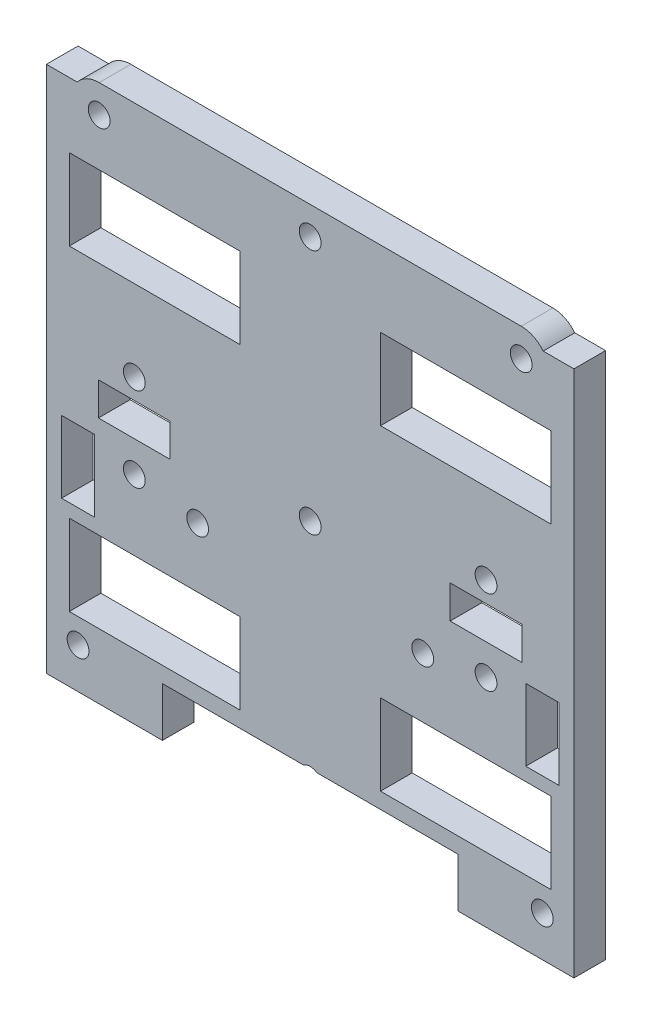
SolidWorks part; units mm, degrees
ref_plane "Front Plane" through (0, 0, 0) normal (0, 0, 1) x (1, 0, 0)
ref_plane "Top Plane" through (0, 0, 0) normal (0, 1, 0) x (1, 0, 0)
ref_plane "Right Plane" through (0, 0, 0) normal (1, 0, 0) x (0, 0, -1)
sketch "Sketch1" plane through (0, 0, 0) normal (0, 0, 1) x (1, 0, 0)
  line L0 (0, -37.5) -> (0, 37.5) construction
  line L1 (-47.5, -37.5) -> (47.5, -37.5)
  line L2 (-47.5, -37.5) -> (-47.5, 37.5)
  line L3 (-47.5, 37.5) -> (47.5, 37.5)
  line L4 (47.5, -37.5) -> (47.5, 37.5)
  line L5 (-47.5, -37.5) -> (47.5, 37.5) construction
  line L6 (-47.5, 37.5) -> (47.5, -37.5) construction
  line L7 (-47.5, 0) -> (47.5, 0) construction
  line L8 (-47.5, 22.5) -> (47.5, 22.5) construction
  line L9 (34.25, 16.75) -> (10, 28.25) construction
  line L10 (-34.25, 28.25) -> (-10, 28.25)
  line L11 (-34.25, 28.25) -> (-34.25, 16.75)
  line L12 (-34.25, 16.75) -> (-10, 16.75)
  line L13 (-10, 28.25) -> (-10, 16.75)
  line L14 (-34.25, 28.25) -> (-10, 16.75) construction
  line L15 (-34.25, 16.75) -> (-10, 28.25) construction
  line L16 (34.25, 28.25) -> (10, 16.75) construction
  line L17 (10, 28.25) -> (10, 16.75)
  line L18 (34.25, 16.75) -> (10, 16.75)
  line L19 (34.25, 28.25) -> (34.25, 16.75)
  line L20 (34.25, 28.25) -> (10, 28.25)
  line L21 (34.25, -28.25) -> (10, -16.75) construction
  line L22 (-34.25, -16.75) -> (-10, -28.25) construction
  line L23 (-34.25, -28.25) -> (-10, -16.75) construction
  line L24 (34.25, -16.75) -> (10, -28.25) construction
  line L25 (34.25, -28.25) -> (10, -28.25)
  line L26 (34.25, -28.25) -> (34.25, -16.75)
  line L27 (34.25, -16.75) -> (10, -16.75)
  line L28 (10, -28.25) -> (10, -16.75)
  line L29 (-10, -28.25) -> (-10, -16.75)
  line L30 (-34.25, -16.75) -> (-10, -16.75)
  line L31 (-34.25, -28.25) -> (-34.25, -16.75)
  line L32 (-34.25, -28.25) -> (-10, -28.25)
  point P0 (0, 0)
  point P12 (-22.125, 22.5)
  point P21 (22.125, 22.5)
  point P30 (22.125, -22.5)
  point P31 (-22.125, -22.5)
  dimension "D1" = 95
  dimension "D2" = 75
  dimension "D3" = 22.5
  dimension "D4" = 24.25
  dimension "D5" = 11.5
  dimension "D6" = 10
extrude "Boss-Extrude1" add sketch "Sketch1" along normal blind 4.5
sketch "Sketch8" plane through (0, 0, 4.5) normal (0, 0, 1) x (1, 0, 0)
  line L0 (-47.5, 37.5) -> (-47.5, -37.5) construction
  line L1 (47.5, -37.5) -> (47.5, 37.5) construction
  circle A0 centre (-47.5, 29.5) radius 8
  circle A1 centre (47.5, 29.5) radius 8
  dimension "D1" = 16
extrude "Boss-Extrude2" [suppressed] add sketch "Sketch8" against normal through all
sketch "Sketch2" plane through (0, 0, 4.5) normal (0, 0, 1) x (1, 0, 0)
  line L0 (0, -37.5) -> (0, 37.5) construction
  line L1 (-47.5, -37.5) -> (47.5, -37.5) construction
  line L2 (47.5, 37.5) -> (-47.5, 37.5) construction
  line L3 (-47.5, 0) -> (47.5, 0) construction
  line L4 (-47.5, 37.5) -> (-47.5, -37.5) construction
  line L5 (47.5, -37.5) -> (47.5, 37.5) construction
  line L6 (-40, 0) -> (40, 0) construction
  line L7 (-30, 35) -> (30, 35) construction
  circle A0 centre (-30, 35) radius 1.55
  circle A1 centre (30, 35) radius 1.55
  circle A2 centre (40, 0) radius 1.55
  circle A3 centre (-40, 0) radius 1.55
  circle A4 centre (0, 35) radius 1.55
  dimension "D1" = 3.1
  dimension "D7" = 3.1
  dimension "D8" = 3.1
  dimension "D9" = 3.1
  dimension "D2" = 30
  dimension "D3" = 35
  dimension "D4" = 80
  dimension "D5" = 40
  dimension "D6" = 0
extrude "screwHoles" cut sketch "Sketch2" against normal through all
sketch "Sketch3" plane through (0, 0, 4.5) normal (0, 0, 1) x (1, 0, 0)
  line L0 (-47.5, -20) -> (26.0486, -20) construction
  line L1 (-47.5, 37.5) -> (-47.5, -37.5) construction
  line L3 (0, 37.5) -> (0, -37.5) construction
  line L4 (47.5, 37.5) -> (-47.5, 37.5) construction
  line L5 (-47.5, -37.5) -> (47.5, -37.5) construction
  line L6 (19.1, -22.35) -> (8.9, -17.65) construction
  line L7 (-19.1, -17.65) -> (-8.9, -17.65)
  line L8 (-19.1, -17.65) -> (-19.1, -22.35)
  line L9 (-19.1, -22.35) -> (-8.9, -22.35)
  line L10 (-8.9, -17.65) -> (-8.9, -22.35)
  line L11 (-19.1, -17.65) -> (-8.9, -22.35) construction
  line L12 (-19.1, -22.35) -> (-8.9, -17.65) construction
  line L13 (19.1, -17.65) -> (8.9, -22.35) construction
  line L14 (8.9, -17.65) -> (8.9, -22.35)
  line L15 (19.1, -22.35) -> (8.9, -22.35)
  line L16 (19.1, -17.65) -> (19.1, -22.35)
  line L17 (19.1, -17.65) -> (8.9, -17.65)
  line L18 (-47.5, 37.5) -> (-47.5, -37.5) construction
  point P2 (-47.5, 0)
  point P12 (-14, -20)
  point P21 (14, -20)
  dimension "D1" = 10.2
  dimension "D2" = 4.7
  dimension "D3" = 14
  dimension "D4" = 20
extrude "BeltClamp" [suppressed] cut sketch "Sketch3" against normal through all
sketch "Sketch4" plane through (0, 0, 4.5) normal (0, 0, 1) x (1, 0, 0)
  line L0 (-47.5, 0) -> (47.5, 0) construction
  line L1 (-47.5, 37.5) -> (-47.5, -37.5) construction
  line L2 (47.5, -37.5) -> (47.5, 37.5) construction
  line L3 (0, 0) -> (0, 33.45) construction
  line L4 (-30.1, 2.35) -> (-19.9, 2.35)
  line L5 (-30.1, 2.35) -> (-30.1, -2.35)
  line L6 (-30.1, -2.35) -> (-19.9, -2.35)
  line L7 (-19.9, 2.35) -> (-19.9, -2.35)
  line L8 (-30.1, 2.35) -> (-19.9, -2.35) construction
  line L9 (-30.1, -2.35) -> (-19.9, 2.35) construction
  line L10 (30.1, -2.35) -> (19.9, 2.35) construction
  line L11 (30.1, 2.35) -> (19.9, -2.35) construction
  line L12 (19.9, 2.35) -> (19.9, -2.35)
  line L13 (30.1, -2.35) -> (19.9, -2.35)
  line L14 (30.1, 2.35) -> (30.1, -2.35)
  line L15 (30.1, 2.35) -> (19.9, 2.35)
  line L16 (-30.1, -2.35) -> (-19.9, 2.35) construction
  circle A0 centre (-40, 0) radius 1.55 construction
  circle A1 centre (0, 35) radius 1.55 construction
  circle A2 centre (0, 0) radius 1.55
  point P6 (-25, 0)
  point P22 (25, 0)
  dimension "D1" = 10.2
  dimension "D2" = 4.7
  dimension "D5" = 3.1
  dimension "D3" = 0
  dimension "D4" = 25
extrude "Cut-Extrude3" cut sketch "Sketch4" against normal through all
sketch "Sketch5" plane through (0, 0, 4.5) normal (0, 0, 1) x (1, 0, 0)
  line L0 (-47.5, -9.75) -> (47.5, -9.75) construction
  line L1 (-47.5, 37.5) -> (-47.5, -37.5) construction
  line L2 (47.5, -37.5) -> (47.5, 37.5) construction
  line L4 (0, -37.5) -> (0, 37.5) construction
  line L5 (-47.5, -37.5) -> (47.5, -37.5) construction
  line L6 (47.5, 37.5) -> (-47.5, 37.5) construction
  line L7 (-30.65, -14.85) -> (-35.35, -4.65) construction
  line L8 (30.65, -4.65) -> (35.35, -4.65)
  line L9 (30.65, -4.65) -> (30.65, -14.85)
  line L10 (30.65, -14.85) -> (35.35, -14.85)
  line L11 (35.35, -4.65) -> (35.35, -14.85)
  line L12 (30.65, -4.65) -> (35.35, -14.85) construction
  line L13 (30.65, -14.85) -> (35.35, -4.65) construction
  line L14 (-30.65, -4.65) -> (-35.35, -14.85) construction
  line L15 (-35.35, -4.65) -> (-35.35, -14.85)
  line L16 (-30.65, -14.85) -> (-35.35, -14.85)
  line L17 (-30.65, -4.65) -> (-30.65, -14.85)
  line L18 (-30.65, -4.65) -> (-35.35, -4.65)
  line L19 (33, -9.75) -> (33, -37.5) construction
  line L20 (-33, -9.75) -> (-33, -37.5) construction
  line L21 (-33, -31.75) -> (33, -31.75) construction
  circle A0 centre (33, -31.75) radius 1.55
  circle A1 centre (-33, -31.75) radius 1.55
  circle A2 centre (0, -31.75) radius 1.55
  point P15 (33, -9.75)
  point P24 (-33, -9.75)
  dimension "D7" = 3.1
  dimension "D5" = 3.1
  dimension "D2" = 10.2
  dimension "D3" = 4.7
  dimension "D4" = 33
  dimension "D6" = 22
  dimension "D1" = 9.75
extrude "Cut-Extrude4" cut sketch "Sketch5" against normal through all
sketch "Sketch9" plane through (0, 0, 4.5) normal (0, 0, 1) x (1, 0, 0)
  line L0 (47.5, 37.5) -> (-47.5, 37.5) construction
  line L1 (0, 37.5) -> (0, -37.5) construction
  line L2 (-47.5, -37.5) -> (47.5, -37.5) construction
  line L3 (50.5, 35) -> (45.5, 35) construction
  line L4 (-50.5, 35) -> (-45.5, 35) construction
  circle A0 centre (-30, 35) radius 4
  circle A1 centre (-30, 35) radius 1.55
  circle A2 centre (-30, 35) radius 1.55 construction
  circle A3 centre (30, 35) radius 1.55
  circle A4 centre (30, 35) radius 4
  point P17 (0, -37.5)
  dimension "D1" = 8
extrude "Boss-Extrude3" add sketch "Sketch9" against normal through all
sketch "Sketch10" plane through (0, 0, 4.5) normal (0, 0, 1) x (1, 0, 0)
  line L0 (-60, 37.5) -> (-37.5, 37.5)
  line L1 (-37.5, 37.5) -> (-37.5, -37.5)
  line L2 (-47.5, -37.5) -> (47.5, -37.5) construction
  line L3 (-37.5, -37.5) -> (-60, -37.5)
  line L4 (-60, -37.5) -> (-60, 37.5)
  line L5 (0, 37.5) -> (0, -37.5) construction
  line L6 (26.8775, 37.5) -> (-26.8775, 37.5) construction
  line L7 (60, -37.5) -> (60, 37.5)
  line L8 (37.5, -37.5) -> (60, -37.5)
  line L9 (37.5, 37.5) -> (37.5, -37.5)
  line L10 (60, 37.5) -> (37.5, 37.5)
  line L11 (-60, -37.5) -> (-60, 37.5)
  line L12 (-33.1225, 37.5) -> (-47.5, 37.5) construction
  line M3 (47.5, -37.5) -> (47.5, 37.5)
  line M7 (-47.5, 37.5) -> (-47.5, -37.5)
  line M8 (-47.5, -37.5) -> (47.5, -37.5)
  dimension "D3" = 0
  dimension "D1" = 75
  dimension "D2" = 60
extrude "Cut-Extrude5" cut sketch "Sketch10" against normal through all contours L1 L0 M7 M8 | L10 L9 M3 M8 region at (42.5, 0, 4.5) region at (-42.5, 0, 4.5)
sketch "Sketch11" plane through (0, 0, 4.5) normal (0, 0, 1) x (1, 0, 0)
  line L0 (-30, 39) -> (30, 39)
  line L1 (30, 39) -> (26.8775, 37.5)
  line L2 (26.8775, 37.5) -> (-26.8775, 37.5)
  line L3 (-26.8775, 37.5) -> (-30, 39)
  arc A0 (-26.8775, 37.5) -> (-33.1225, 37.5) centre (-30, 35) ccw construction
  arc A1 (33.1225, 37.5) -> (26.8775, 37.5) centre (30, 35) ccw construction
extrude "Boss-Extrude4" add sketch "Sketch11" against normal through all
sketch "Sketch12" plane through (0, 0, 4.5) normal (0, 0, 1) x (1, 0, 0)
  line L0 (-37.5, -8.25) -> (37.5, -8.25) construction
  line L1 (-37.5, 37.5) -> (-37.5, -37.5) construction
  line L2 (37.5, 37.5) -> (37.5, -37.5) construction
  line L3 (0, 0) -> (0, -37.5) construction
  line L4 (-37.5, -37.5) -> (37.5, -37.5) construction
  circle A0 centre (-16, -8.25) radius 1.55
  circle A1 centre (16, -8.25) radius 1.55
  dimension "D2" = 3.1
  dimension "D1" = 16
  dimension "D3" = 8.25
extrude "FanBraceScrews" cut sketch "Sketch12" against normal through all
sketch "Sketch13" plane through (0, 0, 4.5) normal (0, 0, 1) x (1, 0, 0)
  line L0 (-37.5, -37.5) -> (37.5, -37.5) construction
  line L1 (-21, -44.5) -> (21, -44.5)
  line L2 (-21, -44.5) -> (-21, -30.5)
  line L3 (-21, -30.5) -> (21, -30.5)
  line L4 (21, -44.5) -> (21, -30.5)
  line L5 (-21, -44.5) -> (21, -30.5) construction
  line L6 (-21, -30.5) -> (21, -44.5) construction
  point P0 (0, -37.5)
  dimension "D1" = 42
  dimension "D2" = 7
extrude "Cut-Extrude7" cut sketch "Sketch13" against normal through all
sketch "Sketch14" plane through (0, 0, 4.5) normal (0, 0, 1) x (1, 0, 0)
  line L0 (16, -9.8) -> (16, 3.75) construction
  line L1 (0, 0) -> (0, -40.3958) construction
  line L2 (-16, -9.8) -> (-16, 3.75) construction
  circle A0 centre (16, -8.25) radius 1.55 construction
  circle A1 centre (16, 3.75) radius 1.55
  circle A2 centre (-16, 3.75) radius 1.55
  dimension "D2" = 3.1
  dimension "D1" = 12
extrude "Cut-Extrude8" [suppressed] cut sketch "Sketch14" against normal through all
sketch "Sketch15" plane through (0, 0, 4.5) normal (0, 0, 1) x (1, 0, 0)
  line L0 (-25, 5.25) -> (-25, -6.75) construction
  line L2 (0, 0) -> (0, -11.0705) construction
  line L3 (16, -8.3509) -> (25, -6.75) construction
  line L4 (25, 5.25) -> (25, -6.75) construction
  circle A0 centre (-25, 5.25) radius 1.55
  circle A1 centre (-25, -6.75) radius 1.55
  circle A2 centre (25, -6.75) radius 1.55
  circle A3 centre (25, 5.25) radius 1.55
  circle A5 centre (-16, -8.25) radius 1.55 construction
  dimension "D1" = 12
  dimension "D3" = 3.1
  dimension "D4" = 3.1
  dimension "D2" = 25
  dimension "D5" = 1.5
extrude "BeltClipScrews" cut sketch "Sketch15" against normal through all
equation "\"X-ROD-SPACING\"=45"
equation "\"Y-ROD-SPACING\"=75"
equation "\"Z-ROD-SPACING\"=17.5"
equation "\"Y-BED-OFFSET\"=2"
equation "\"Y-BED-ROD-INSET\"=3.5"
equation "\"Y-BED-SCREW-SPACING\"=209"
equation "\"Y-BED-SCREW-CUTOUT-SLOT-HEIGHT\"=2"
equation "\"T-SLOT-NUT-FILLET-RADIUS\"=0.25"
equation "\"T-SLOT-SCREW-SHAFT-RADIUS\"=1.75"
equation "\"T-SLOT-SCREW-SHAFT-CUTOUT-LENGTH\"=10.5"
equation "\"T-SLOT-NUT-DEPTH\"=4.2"
equation "\"T-SLOT-NUT-WIDTH\"=3"
equation "\"T-SLOT-NUT-END-DISTANCE\"=8"
equation "\"ACRYLIC-THICKNESS\"=10"
equation "\"ACRYLIC-THICKNESS2\"=4.5"
equation "\"ACRYLIC-TAB-CUTOUT-SIZE\"=\"ACRYLIC-THICKNESS\"+\"ACRYLIC-TAB-TOLERANCE\"*2"
equation "\"ACRYLIC-TAB-WIDTH\"=\"ACRYLIC-THICKNESS\""
equation "\"ACRYLIC-M3-HOLE\"=3.1"
equation "\"SMOOTHROD-CAP-SCREW-DISTANCE\"=20"
equation "\"FRAME-WIDTH-INNER\"=370"
equation "\"NEMA17-HOLE-SPACING\"=31"
equation "\"NEMA17-CENTRAL-CUTOUT\"=22.5"
equation "\"Z-BRACKET-REACH\"=55"
equation "\"Z-ROD-INSET\"=16"
equation "\"TOP-BRACKET-SPACING\"=40"
equation "\"SMOOTHROD-X-LENGTH\"=350"
equation "\"SMOOTHROD-Y-LENGTH\"=350"
equation "\"SMOOTHROD-Z-LENGTH\"=350"
equation "\"SMOOTHROD-TIGHTENING-HEADROOM\"=.25"
equation "\"LEADSCREW-Z-LENGTH\"=300"
equation "\"SCREW-LENGTH-FRAME\"=\"ACRYLIC-THICKNESS\" + 10"
equation "\"SCREW-LENGTH-MOTOR\"=\"ACRYLIC-THICKNESS\" + 5"
equation "\"SCREW-HEAD-RADIUS\"=6"
equation "\"PRINTED-X-SMOOTHROD-DIAMETER\"=8.2"
equation "\"PRINTED-X-SMOOTHROD-CUTOUT\"=10"
equation "\"PRINTED-X-BASE-HEIGHT\"=10"
equation "\"PRINTED-LM8UU-CUTOUT-SIZE\"=15.25"
equation "\"PRINTED-LM8UU-CUTOUT-LENGTH\"=24.5"
equation "\"PRINTED-X-IDLER-HEIGHT\"=16"
equation "\"PSU-MOUNTING-WIDTH\"=95"
equation "\"PSU-MOUNTING-HEIGHT\"=177"
equation "\"Y-BELT-TO-ROD-DISTANCE\"=20"
equation "\"SPOOL-HOLDER-ROD-SPACING\"=150"
equation "\"D3@Sketch1\"=\"X-ROD-SPACING\"/2"
equation "\"D4@Sketch1\"=\"ACRYLIC-X-CARRIAGE-LM8UU-CUTOUT-WIDTH\""
equation "\"D1@Boss-Extrude1\"=\"ACRYLIC-THICKNESS2\""
equation "\"D1@Sketch2\"=\"ACRYLIC-M3-HOLE\""
equation "\"D1@Sketch3\"=\"ACRYLIC-TAB-CUTOUT-SIZE\""
equation "\"D2@Sketch3\"=\"ACRYLIC-THICKNESS2\"+\"ACRYLIC-TAB-TOLERANCE\"*2"
equation "\"ACRYLIC-X-CARRIAGE-WIDTH\"=55"
equation "\"ACRYLIC-X-CARRIAGE-HEIGHT\"=75"
equation "\"D2@Sketch1\"=\"ACRYLIC-X-CARRIAGE-HEIGHT\""
equation "\"ACRYLIC-X-CARRIAGE-CENTER-TAB-SPACING\"=14"
equation "\"D3@Sketch3\"=\"ACRYLIC-X-CARRIAGE-CENTER-TAB-SPACING\""
equation "\"SCREW-LENGTH-EXTRUDER\"=28"
equation "\"ACRYLIC-X-CARRIAGE-SCREW-SPACING-X\"=15"
equation "\"ACRYLIC-X-CARRIAGE-SCREW-SPACING-Y\"=33"
equation "\"D1@Sketch4\"=\"ACRYLIC-TAB-CUTOUT-SIZE\""
equation "\"D2@Sketch4\"=\"ACRYLIC-THICKNESS2\"+\"ACRYLIC-TAB-TOLERANCE\"*2"
equation "\"D2@Sketch5\"=\"ACRYLIC-TAB-CUTOUT-SIZE\""
equation "\"D3@Sketch5\"=\"ACRYLIC-THICKNESS2\"+\"ACRYLIC-TAB-TOLERANCE\"*2"
equation "\"ACRYLIC-X-CARRIAGE-EXTRUDER-SHELF-DEPTH\"=\"ACRYLIC-X-CARRIAGE-EXTRUDER-OFFSET\" + 28"
equation "\"ACRYLIC-X-CARRIAGE-EXTRUDER-BRACE-SPACING\"=23"
equation "\"D4@Sketch5\"=\"ACRYLIC-X-CARRIAGE-DUAL-MOUNT-BRACE-WIDTH\""
equation "\"D1@Sketch5\"=\"ACRYLIC-THICKNESS2\"/2 + 7.5"
equation "\"D4@Sketch2\"=\"ACRYLIC-X-CARRIAGE-DUAL-MOUNT-SCREW-WIDTH\"*2"
equation "\"D5@Sketch2\"=\"ACRYLIC-X-CARRIAGE-DUAL-MOUNT-SCREW-WIDTH\""
equation "\"D7@Sketch2\"=\"ACRYLIC-M3-HOLE\""
equation "\"D8@Sketch2\"=\"ACRYLIC-M3-HOLE\""
equation "\"ACRYLIC-X-CARRIAGE-LM8UU-CUTOUT-WIDTH\"=24.25"
equation "\"ACRYLIC-TAB-TOLERANCE\"=.1"
equation "\"ACRYLIC-X-CARRIAGE-EXTRUDER-OFFSET\"=26"
equation "\"ACRYLIC-X-CARRIAGE-EXTRUDER-ANGLE\"=90"
equation "\"ACRYLIC-X-CARRIAGE-EXTRUDER-BRACE-TAB-OFFSET\"=20"
equation "\"ACRYLIC-X-CARRIAGE-EXTRUDER-BRACE-HEIGHT\"=35"
equation "\"ACRYLIC-X-CARRIAGE-EXTRUDER-BRACE-SCREW-SPACING\"=22"
equation "\"D5@Sketch5\"=\"ACRYLIC-M3-HOLE\""
equation "\"ACRYLIC-X-CARRIAGE-DUAL-WIDTH-MULTIPLIER\"=1.65"
equation "\"ACRYLIC-X-CARRIAGE-DUAL-HOTEND-SPACING\"=42"
equation "\"ACRYLIC-X-CARRIAGE-DUAL-WIDTH\"=75"
equation "\"ACRYLIC-X-CARRIAGE-DUAL-HOTEND-SEPARATION\"=36"
equation "\"ACRYLIC-X-CARRIAGE-DUAL-MOUNT-PLATE-DEPTH\"=75"
equation "\"ACRYLIC-X-CARRIAGE-DUAL-MOUNT-BRACE-WIDTH\"=33"
equation "\"ACRYLIC-X-CARRIAGE-DUAL-MOUNT-SCREW-WIDTH\"=40"
equation "\"D9@Sketch2\"=\"ACRYLIC-M3-HOLE\""
equation "\"D7@Sketch5\"=\"ACRYLIC-M3-HOLE\""
equation "\"ACRYLIC-X-CARRIAGE-LM8UU-CUTOUT-HEIGHT\"=11.5"
equation "\"D5@Sketch1\"=\"ACRYLIC-X-CARRIAGE-LM8UU-CUTOUT-HEIGHT\""
equation "\"D1@Sketch10\"=\"ACRYLIC-X-CARRIAGE-DUAL-WIDTH\""
equation "\"D5@Sketch4\"=\"ACRYLIC-M3-HOLE\""
equation "\"D2@Sketch12\"=\"ACRYLIC-M3-HOLE\""
equation "\"D3@Sketch12\"=\"ACRYLIC-THICKNESS2\"/2 + 6"
equation "\"D2@Sketch14\"=\"ACRYLIC-M3-HOLE\""
equation "\"D3@Sketch15\"=\"ACRYLIC-M3-HOLE\""
equation "\"D4@Sketch15\"=\"ACRYLIC-M3-HOLE\""
